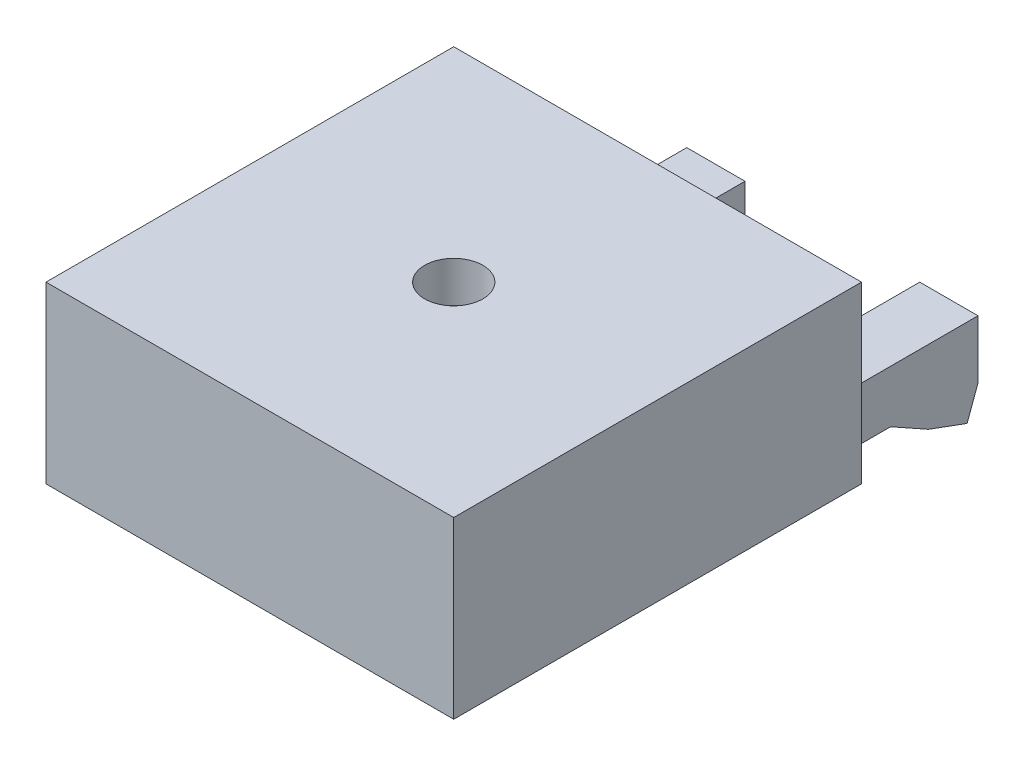
SolidWorks part; units mm, degrees
ref_plane "Plan de face" through (0, 0, 0) normal (0, 0, 1) x (1, 0, 0)
ref_plane "Plan de dessus" through (0, 0, 0) normal (0, 1, 0) x (1, 0, 0)
ref_plane "Plan de droite" through (0, 0, 0) normal (1, 0, 0) x (0, 0, -1)
sketch "Esquisse1" plane through (0, 0, 0) normal (0, 1, 0) x (1, 0, 0)
  line L1 (0, 0) -> (70, 0)
  line L2 (0, 0) -> (0, 70)
  line L3 (0, 70) -> (70, 70)
  line L4 (70, 0) -> (70, 70)
  dimension "D1" = 70
  dimension "D2" = 70
extrude "Boss.-Extru.4" add sketch "Esquisse1" along normal blind 30
sketch "Esquisse5" plane through (0, 0, 0) normal (0, -1, 0) x (-1, 0, 0)
  line L0 (-70, 0) -> (-70, 70) construction
  line L1 (-5, 5) -> (-65, 5)
  line L2 (-5, 5) -> (-5, 65)
  line L3 (-5, 65) -> (-65, 65)
  line L4 (-65, 5) -> (-65, 65)
  line L5 (0, 70) -> (0, 0) construction
  line L6 (0, 0) -> (-70, 0) construction
  line L7 (-70, 70) -> (0, 70) construction
  dimension "D1" = 5
  dimension "D2" = 5
  dimension "D3" = 5
  dimension "D4" = 5
extrude "Enlèv. mat.-Extru.3" cut sketch "Esquisse5" against normal blind 23
sketch "Esquisse6" plane through (0, 23, 0) normal (0, -1, 0) x (-1, 0, 0)
  line L0 (0, 0) -> (-70, 0) construction
  line L1 (0, 70) -> (0, 0) construction
  circle A0 centre (-35, 35) radius 5
  dimension "D1" = 10
  dimension "D2" = 35
  dimension "D3" = 35
extrude "Enlèv. mat.-Extru.4" cut sketch "Esquisse6" against normal blind 23 contours A0
sketch "Esquisse24" plane through (0, 0, -70) normal (0, 0, -1) x (-1, 0, 0)
  line L0 (0, 30) -> (-10.005, 30)
  line L1 (-70, 30) -> (0, 30) construction
  line L2 (-20.005, 30) -> (-50.005, 30)
  line L3 (-50.005, 30) -> (-60.005, 30)
  line L4 (-60.005, 30) -> (-60.005, 0)
  line L5 (-70, 0) -> (0, 0) construction
  line L10 (-60.005, 0) -> (-50.005, 0)
  line L11 (-50.005, 0) -> (-20.005, 0)
  line L12 (-20.005, 0) -> (-10.005, 0)
  dimension "D1" = 10
  dimension "D2" = 10.005
  dimension "D3" = 10
  dimension "D4" = 30
sketch "Esquisse28" plane through (0, 0, 0) normal (0, -1, 0) x (1, 0, 0)
  line L0 (50.005, -70) -> (60.005, -70) construction
  line L1 (50.005, -70) -> (60.005, -70)
  line L2 (50.005, -70) -> (50.005, -100)
  line L3 (50.005, -100) -> (60.005, -100)
  line L4 (60.005, -70) -> (60.005, -100)
  dimension "D1" = 30
extrude "Boss.-Extru.8" add sketch "Esquisse28" along normal mid plane 10
sketch "Esquisse29" plane through (60.005, 0, 0) normal (1, 0, 0) x (0, 0, -1)
  line L0 (70, -5) -> (85, -5)
  line L1 (100, -5) -> (96.4393, -14.671)
  line L2 (100, -5) -> (70, -5) construction
  line L3 (96.4393, -14.671) -> (98.2196, -9.8355)
  line L4 (98.2196, -9.8355) -> (97.3294, -12.2532)
  line L5 (97.3294, -12.2532) -> (85, -5)
  point P8 (97.3294, -12.2532)
  line M5 (70, -5) -> (100, -5)
extrude "Boss.-Extru.9" add sketch "Esquisse29" against normal blind 10 contours L5 L1 M5 region at (60.005, -7.4177, -94.1098)
sketch "Esquisse30" plane through (0, 0, 0) normal (0, -1, 0) x (1, 0, 0)
  line L0 (0, -70) -> (10.005, -70) construction
  line L1 (10.005, -70) -> (20.005, -70)
  line L2 (10.005, -70) -> (10.005, -100)
  line L3 (10.005, -100) -> (20.005, -100)
  line L4 (20.005, -70) -> (20.005, -100)
  dimension "D1" = 30
extrude "Boss.-Extru.10" add sketch "Esquisse30" along normal mid plane 10
sketch "Esquisse39" plane through (10.005, 0, 0) normal (-1, 0, 0) x (0, 0, 1)
  line L0 (-100, -5) -> (-95.9609, -15.2316)
  line L1 (-95.9609, -15.2316) -> (-85, -5)
  line L2 (-70, -5) -> (-100, -5) construction
  line L3 (-85, -5) -> (-100, -5)
  dimension "D1" = 11
extrude "Boss.-Extru.14" add sketch "Esquisse39" against normal blind 10
sketch "Esquisse40" plane through (0, -34.8279, -88.2251) normal (0, -0.3672, -0.9301) x (-1, 0, 0)
  line L0 (-20.005, 21.0679) -> (-20.005, 22.0679)
  line L1 (-20.005, 32.0679) -> (-20.005, 21.0679) construction
  line L2 (-20.005, 22.0679) -> (-10.005, 21.0679)
  line L3 (-10.005, 21.0679) -> (-20.005, 21.0679)
  dimension "D1" = 1
extrude "Enlèv. mat.-Extru.6" cut sketch "Esquisse40" against normal blind 10
sketch "Esquisse41" plane through (0, -33.0203, -89.6833) normal (0, -0.3455, -0.9384) x (-1, 0, 0)
  line L4 (-60.005, 23.13) -> (-60.005, 22.13)
  line L5 (-60.005, 29.8592) -> (-60.005, 22.13) construction
  line L6 (-60.005, 22.13) -> (-50.005, 22.13)
  line L7 (-50.005, 22.13) -> (-60.005, 23.13)
  dimension "D1" = 1
extrude "Enlèv. mat.-Extru.15" cut sketch "Esquisse41" against normal blind 14
sketch "Esquisse43" plane through (0, -33.0203, -89.6833) normal (0, -0.3455, -0.9384) x (-1, 0, 0)
  line L0 (-50.005, 29.8592) -> (-50.005, 23.3298)
  line L1 (-50.005, 29.8592) -> (-50.005, 22.13) construction
  line L2 (-50.005, 23.3298) -> (-60.005, 24.4475)
  line L3 (-60.005, 29.8592) -> (-60.005, 23.13) construction
  line L4 (-60.005, 24.4475) -> (-60.005, 29.8592)
  line L5 (-60.005, 29.8592) -> (-50.005, 29.8592)
  line L6 (-60.005, 23.13) -> (-60.005, 24.4475)
  line L7 (-50.005, 23.3298) -> (-50.005, 22.13)
  line L8 (-50.005, 22.13) -> (-60.005, 23.13)
  line M5 (-60.005, 29.8592) -> (-60.005, 23.13)
  line M6 (-60.005, 23.13) -> (-50.005, 22.13)
  line M7 (-50.005, 22.13) -> (-50.005, 29.8592)
  dimension "D1" = 6.5294
  dimension "D2" = 5.4118
extrude "Enlèv. mat.-Extru.16" cut sketch "Esquisse43" against normal blind 10 contours L2 M7 M5 M6 region at (55.0829, -11.1857, -97.7225)
sketch "Esquisse44" plane through (50.005, 0, 0) normal (-1, 0, 0) x (0, 0, 1)
  line L0 (-70, -5) -> (-70, -4.0027)
  line L1 (-70, -5) -> (-70, 0) construction
  line L2 (-70, -4.0027) -> (-84.9959, -4.0027)
  line L3 (-84.9959, -4.0027) -> (-97.744, -11.1273)
  line L4 (-97.744, -11.1273) -> (-91.5203, -8.8358)
  line L5 (-91.5203, -8.8358) -> (-85, -5)
  line L6 (-85, -5) -> (-70, -5)
extrude "Enlèv. mat.-Extru.17" cut sketch "Esquisse44" against normal blind 10
sketch "Esquisse45" plane through (0, -34.8279, -88.2251) normal (0, -0.3672, -0.9301) x (-1, 0, 0)
  line L0 (-20.005, 22.0679) -> (-20.005, 22.1856)
  line L1 (-20.005, 32.0679) -> (-20.005, 22.0679) construction
  line L2 (-20.005, 22.1856) -> (-10.005, 21.0679)
  line L3 (-10.005, 21.0679) -> (-20.005, 22.0679)
  dimension "D1" = 0.1176
extrude "Enlèv. mat.-Extru.18" cut sketch "Esquisse45" against normal blind 10
